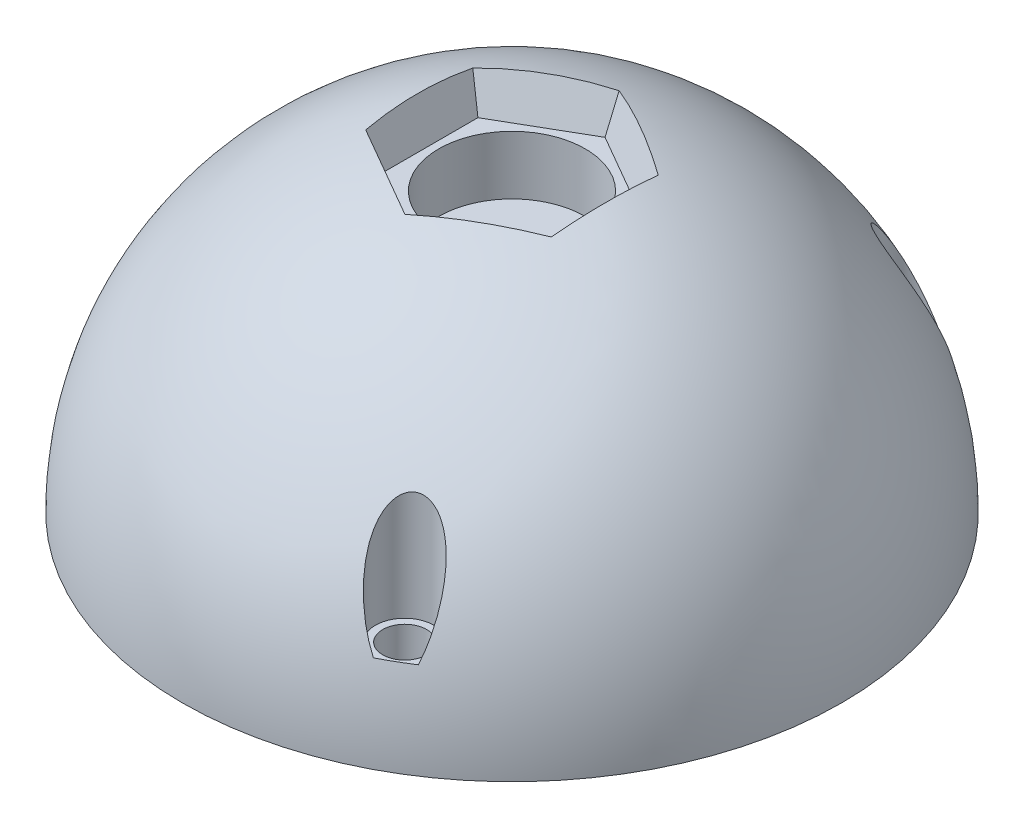
SolidWorks part; units mm, degrees
ref_plane "前视基准面" through (0, 0, 0) normal (0, 0, 1) x (1, 0, 0)
ref_plane "上视基准面" through (0, 0, 0) normal (0, 1, 0) x (1, 0, 0)
ref_plane "右视基准面" through (0, 0, 0) normal (1, 0, 0) x (0, 0, -1)
sketch "草图1" plane through (0, 0, 0) normal (0, 0, 1) x (1, 0, 0)
  line L0 (0, 0) -> (-22.5, 0)
  line L2 (0, 0) -> (22.5, 0)
  arc A0 (-22.5, 0) -> (0, 22.5) centre (0, 0) cw
  arc A1 (0, 22.5) -> (22.5, 0) centre (0, 0) cw
  dimension "D1" = 22.5
revolve "旋转2" add sketch "草图1" angle 360 about L0
sketch "草图5" plane through (0, 0, 0) normal (0, 1, 0) x (1, 0, 0)
  circle A0 centre (0, 0) radius 17.5
  dimension "D1" = 35
extrude "切除-拉伸2" cut sketch "草图5" against normal blind 5 and the other way blind 10
ref_plane "基准面1" through (0, 8, 0) normal (0, 1, 0) x (1, 0, 0)
sketch "草图7" plane through (0, 0, 0) normal (0, 1, 0) x (1, 0, 0)
  line L0 (0, 0) -> (-29.3651, 0) construction
  circle A0 centre (-20, 0) radius 1.5
  dimension "D1" = 3
  dimension "D2" = 20
extrude "切除-拉伸3" cut sketch "草图7" against normal mid plane 10
ref_plane "基准面2" through (0, 15, 0) normal (0, -1, 0) x (-1, 0, 0)
sketch "草图8" plane through (0, 15, 0) normal (0, -1, 0) x (-1, 0, 0)
  circle A0 centre (20, 0) radius 2
  point P4 (0, 0)
  dimension "D1" = 4
  dimension "D2" = 20
extrude "切除-拉伸6" cut sketch "草图8" along normal blind 9
sketch "草图9" plane through (0, -5, 0) normal (0, 1, 0) x (1, 0, 0)
  circle A0 centre (-20, 0) radius 1.5
  dimension "D1" = 3
extrude "凸台-拉伸1" add sketch "草图9" along normal blind 5
sketch "草图10" plane through (0, 0, 0) normal (0, 0, 1) x (1, 0, 0)
  line L0 (0, -23.7557) -> (0, 23.6331) construction
  line L1 (-16, 12.816) -> (-16, 5.985)
  line L5 (-16, 5.985) -> (0, 5.985)
  line L6 (0, 20.5) -> (0, 5.985)
  line L7 (20.5, 0) -> (33.947, 0) construction
  line L8 (0, -5.985) -> (0, -20.5)
  line L9 (-16, -12.816) -> (-16, -5.985)
  line L10 (-16, -5.985) -> (0, -5.985)
  line L11 (-16, 6) -> (-10.3748, 6) construction
  arc A0 (-16, -12.816) -> (0, -20.5) centre (0, 0) ccw
  arc A1 (0, 20.5) -> (-16, 12.816) centre (0, 0) ccw
  point P14 (0, 5.985)
  dimension "D1" = 41
  dimension "D2" = 32
revolve "切除-旋转1" cut sketch "草图10" angle 360 about L6
sketch "草图11" plane through (0, 6, 0) normal (0, 1, 0) x (1, 0, 0)
  circle A0 centre (-20, 0) radius 1.5
  circle A1 centre (-20, 0) radius 1.5 construction
  point P3 (0, 0)
  point P4 (0, 0)
  dimension "D1" = 3
extrude "切除-拉伸7" cut sketch "草图11" against normal blind 5
sketch "草图19" plane through (0, 10, 0) normal (0, -1, 0) x (1, 0, 0)
  circle A0 centre (0, 0) radius 16
extrude "凸台-拉伸3" add sketch "草图19" against normal blind 2
sketch "草图12" plane through (0, -5, 0) normal (0, 1, 0) x (1, 0, 0)
  circle A0 centre (0, 0) radius 5
  dimension "D1" = 10
pattern_circular "阵列(圆周)1" count 3 over 360 about axis through (0, -5, 0) along (0, 1, 0) of "切除-拉伸3", "切除-拉伸6", "凸台-拉伸1", "切除-拉伸7"
sketch "草图13" plane through (0, 0, 0) normal (0, 1, 0) x (1, 0, 0)
  line L6 (-29.6195, 28.0305) -> (29.6195, -28.0305) construction
  circle A0 centre (0, 0) radius 22.5
  point P0 (0, 0)
split "分割2" trim tools "上视基准面" bodies to split 117 resulting bodies 118
ref_plane "基准面3" through (0, 13, 0) normal (0, -1, 0) x (-1, 0, 0)
sketch "草图14" plane through (0, 13, 0) normal (0, -1, 0) x (-1, 0, 0)
  line L1 (0, 8.6603) -> (-7.5, 4.3301)
  line L2 (-7.5, 4.3301) -> (-7.5, -4.3301)
  line L3 (-7.5, -4.3301) -> (0, -8.6603)
  line L4 (0, -8.6603) -> (7.5, -4.3301)
  line L5 (7.5, -4.3301) -> (7.5, 4.3301)
  line L6 (7.5, 4.3301) -> (0, 8.6603)
  circle A0 centre (0, 0) radius 7.5 construction
  point P11 (7.5, 0)
  point P12 (-7.5, 0)
  dimension "D1" = 15
extrude "凸台-拉伸2" add sketch "草图14" against normal up to next draft 20 draft outward yes
ref_plane "基准面4" through (0, 19, 0) normal (0, -1, 0) x (-1, 0, 0)
sketch "草图15" plane through (0, 19, 0) normal (0, -1, 0) x (-1, 0, 0)
  line L12 (0, 6.3509) -> (-5.5, 3.1754)
  line L13 (-5.5, 3.1754) -> (-5.5, -3.1754)
  line L14 (-5.5, -3.1754) -> (0, -6.3509)
  line L15 (0, -6.3509) -> (5.5, -3.1754)
  line L16 (5.5, -3.1754) -> (5.5, 3.1754)
  line L17 (5.5, 3.1754) -> (0, 6.3509)
  line L18 (0, 6.3509) -> (-5.5, 3.1754)
  line L19 (-5.5, 3.1754) -> (-5.5, -3.1754)
  line L20 (-5.5, -3.1754) -> (0, -6.3509)
  line L21 (0, -6.3509) -> (5.5, -3.1754)
  line L22 (5.5, -3.1754) -> (5.5, 3.1754)
  line L23 (5.5, 3.1754) -> (0, 6.3509)
  dimension "D1" = 2
extrude "切除-拉伸9" cut sketch "草图15" against normal blind 10 draft 20 draft outward yes
sketch "草图16" plane through (0, 19, 0) normal (0, 1, 0) x (1, 0, 0)
  circle A0 centre (0, 0) radius 5
  dimension "D1" = 10
extrude "切除-拉伸10" cut sketch "草图16" against normal blind 4
sketch "草图17" plane through (0, 15, 0) normal (0, 1, 0) x (1, 0, 0)
  circle A0 centre (0, 0) radius 0.5
  circle A1 centre (4.5, 0) radius 0.5
  circle A3 centre (0, 0) radius 5 construction
  dimension "D1" = 1
extrude "切除-拉伸11" cut sketch "草图17" against normal blind 2
sketch "草图18" plane through (0, 10, 0) normal (0, -1, 0) x (1, 0, 0)
  circle A0 centre (0, 0) radius 5
  dimension "D1" = 10
extrude "切除-拉伸12" cut sketch "草图18" against normal blind 2
